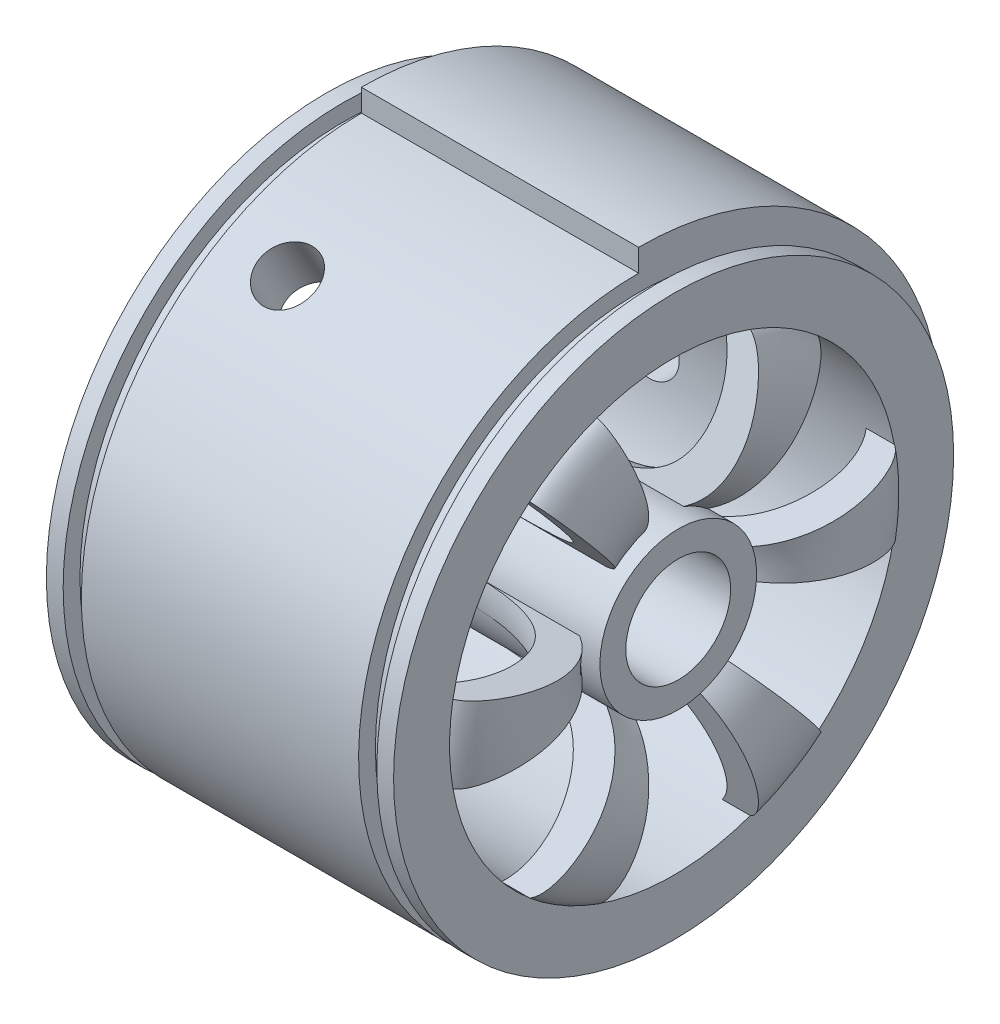
SolidWorks part; units mm, degrees
ref_plane "Front Plane" through (0, 0, 0) normal (0, 0, 1) x (1, 0, 0)
ref_plane "Top Plane" through (0, 0, 0) normal (0, 1, 0) x (1, 0, 0)
ref_plane "Right Plane" through (0, 0, 0) normal (1, 0, 0) x (0, 0, -1)
sketch "Sketch1" plane through (0, 0, 0) normal (0, 0, 1) x (1, 0, 0)
  line L0 (0, 0) -> (49.179, 0) construction
  line L2 (28, 50) -> (28, 47)
  line L3 (-31, 50) -> (-28, 50)
  line L4 (-31, 50) -> (-31, 40)
  line L5 (-31, 40) -> (26, 40)
  line L6 (31, 50) -> (31, 40)
  line L7 (28, 47) -> (24.75, 47)
  line L8 (24.75, 47) -> (24.75, 50)
  line L9 (28, 50) -> (31, 50)
  line L10 (-28, 50) -> (-28, 47)
  line L11 (-28, 47) -> (-24.75, 47)
  line L12 (-24.75, 47) -> (-24.75, 50)
  line L13 (-24.75, 50) -> (24.75, 50)
  line L15 (9.8249, 13.995) -> (9.8249, 9.3629)
  spline S0 degree 3 poles (31, 40) (33.5665, 38.6761) (37.0293, 28.2248) (31.1782, 14.2608) (20.4845, 10.2538) (12.4993, 9.5146) (9.8249, 9.3629) knots 0 0 0 0 0.287846 0.460109 0.693768 0.818804 0.818804 0.818804 0.818804
  spline S1 degree 3 poles (26, 40) (30.7736, 34.2439) (29.4584, 17.5157) (16.1659, 14.3384) (10.5858, 14.0242) (9.8249, 13.995) knots 0 0 0 0 0.466678 0.747183 0.791718 0.791718 0.791718 0.791718
  dimension "D1" = 62
  dimension "D2" = 10
  dimension "D4" = 50
  dimension "D5" = 3
  dimension "D6" = 3
  dimension "D7" = 3.25
  dimension "D8" = 3
  dimension "D9" = 3
  dimension "D10" = 3.25
  dimension "D13" = 5
revolve "Revolve1" add sketch "Sketch1" angle 360 about L0
sketch "Sketch2" plane through (9.8249, 0, 0) normal (-1, 0, 0) x (0, 0, 1)
  circle A0 centre (0, 0) radius 13.995
  circle A1 centre (0, 0) radius 9.3629
extrude "Boss-Extrude1" add sketch "Sketch2" against normal blind 22
sketch "Sketch4" plane through (-31, 0, 0) normal (-1, 0, 0) x (0, 0, 1)
  line L0 (-4.7866, 13.151) -> (-13.6808, 37.5877)
  line L1 (4.7866, 13.151) -> (13.6808, 37.5877)
  line L2 (0, 13.995) -> (0, 40) construction
  arc A3 (4.7866, 13.151) -> (-4.7866, 13.151) centre (0, 0) ccw
  arc A4 (13.6808, 37.5877) -> (-13.6808, 37.5877) centre (0, 0) ccw
  dimension "D1" = 40
  dimension "D2" = 20
extrude "Cut-Extrude1" cut sketch "Sketch4" against normal through all
pattern_circular "CirPattern1" count 6 over 360 about axis through (0, 0, 0) along (-1, 0, 0) of "Cut-Extrude1"
sketch "Sketch5" plane through (0, 0, 0) normal (0, 0, 1) x (1, 0, 0)
  line L0 (26, 0) -> (-31, 0) construction
  circle A0 centre (-13, 0) radius 5
  dimension "D1" = 10
  dimension "D2" = 0
  dimension "D4" = 13
extrude "Cut-Extrude2" cut sketch "Sketch5" against normal through all
pattern_circular "CirPattern2" count 3 over 360 of "Cut-Extrude2"
sketch "Sketch6" plane through (0, 0, 0) normal (0, 0, 1) x (1, 0, 0)
  line L1 (-24.75, 50) -> (24.75, 50)
  line L2 (-24.75, 50) -> (-24.75, 54)
  line L3 (-24.75, 54) -> (24.75, 54)
  line L4 (24.75, 50) -> (24.75, 54)
  dimension "D1" = 24.75
  dimension "D2" = 4
revolve "Revolve2" add sketch "Sketch6" angle 80 about axis through (0, 0, 0) along (-1, 0, 0)
sketch "Sketch8" plane through (9.8249, 0, 0) normal (-1, 0, 0) x (0, 0, 1)
  circle A0 centre (0, 0) radius 9.3629 construction
  circle A1 centre (0, 0) radius 9.3629
  arc A3 (4.7866, 13.151) -> (-4.7866, 13.151) centre (0, 0) ccw
  arc A4 (4.7866, 13.151) -> (-4.7866, 13.151) centre (0, 0) ccw
  arc A16 (-4.7866, 13.151) -> (-8.9958, 10.7208) centre (0, 0) ccw
  arc A17 (-4.7866, 13.151) -> (-8.9958, 10.7208) centre (0, 0) ccw
  arc A18 (-8.9958, 10.7208) -> (-13.7824, 2.4302) centre (0, 0) ccw
  arc A19 (-8.9958, 10.7208) -> (-13.7824, 2.4302) centre (0, 0) ccw
  arc A20 (-13.7824, 2.4302) -> (-13.7824, -2.4302) centre (0, 0) ccw
  arc A21 (-13.7824, 2.4302) -> (-13.7824, -2.4302) centre (0, 0) ccw
  arc A22 (-13.7824, -2.4302) -> (-8.9958, -10.7208) centre (0, 0) ccw
  arc A23 (-13.7824, -2.4302) -> (-8.9958, -10.7208) centre (0, 0) ccw
  arc A24 (-8.9958, -10.7208) -> (-4.7866, -13.151) centre (0, 0) ccw
  arc A25 (-8.9958, -10.7208) -> (-4.7866, -13.151) centre (0, 0) ccw
  arc A26 (-4.7866, -13.151) -> (4.7866, -13.151) centre (0, 0) ccw
  arc A27 (-4.7866, -13.151) -> (4.7866, -13.151) centre (0, 0) ccw
  arc A28 (4.7866, -13.151) -> (8.9958, -10.7208) centre (0, 0) ccw
  arc A29 (4.7866, -13.151) -> (8.9958, -10.7208) centre (0, 0) ccw
  arc A30 (8.9958, -10.7208) -> (13.7824, -2.4302) centre (0, 0) ccw
  arc A31 (8.9958, -10.7208) -> (13.7824, -2.4302) centre (0, 0) ccw
  arc A32 (13.7824, -2.4302) -> (13.7824, 2.4302) centre (0, 0) ccw
  arc A33 (13.7824, -2.4302) -> (13.7824, 2.4302) centre (0, 0) ccw
  arc A34 (13.7824, 2.4302) -> (8.9958, 10.7208) centre (0, 0) ccw
  arc A35 (13.7824, 2.4302) -> (8.9958, 10.7208) centre (0, 0) ccw
  arc A36 (8.9958, 10.7208) -> (4.7866, 13.151) centre (0, 0) ccw
  arc A37 (8.9958, 10.7208) -> (4.7866, 13.151) centre (0, 0) ccw
  dimension "D1" = 0
extrude "Boss-Extrude2" add sketch "Sketch8" along normal blind 10
